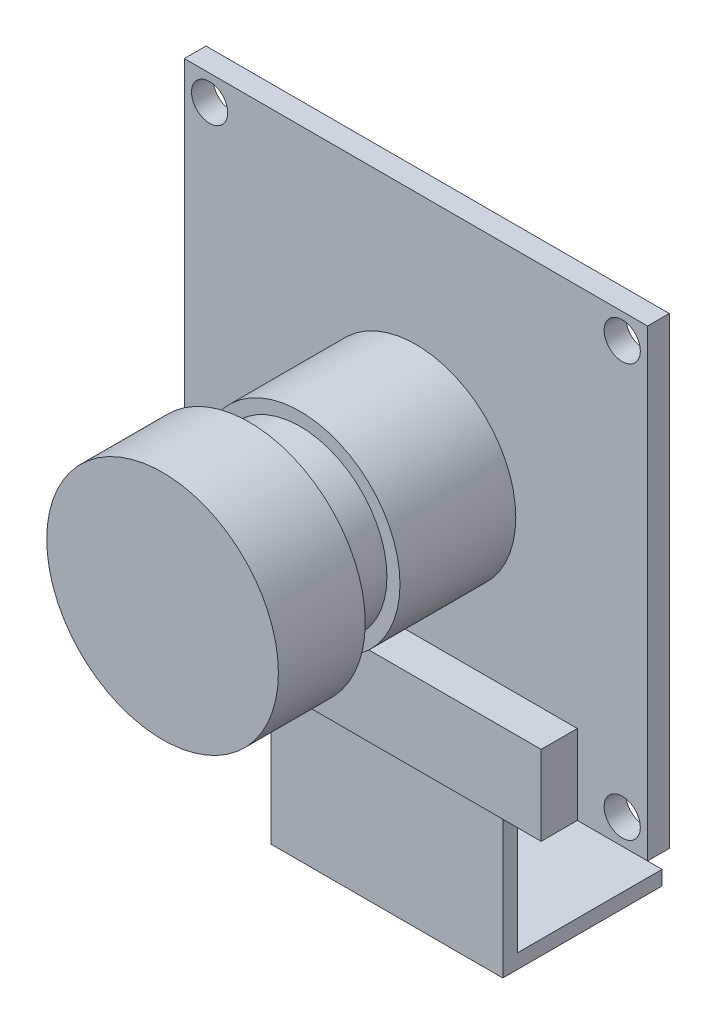
SolidWorks part; units mm, degrees
ref_plane "Спереди" through (0, 0, 0) normal (0, 0, 1) x (1, 0, 0)
ref_plane "Сверху" through (0, 0, 0) normal (0, 1, 0) x (1, 0, 0)
ref_plane "Справа" through (0, 0, 0) normal (1, 0, 0) x (0, 0, -1)
sketch "Эскиз1" plane through (0, 0, 0) normal (0, 0, 1) x (1, 0, 0)
  line L0 (0, 16) -> (0, -16) construction
  line L1 (-16, 16) -> (16, 16)
  line L2 (-16, 16) -> (-16, -16)
  line L3 (-16, -16) -> (16, -16)
  line L4 (16, 16) -> (16, -16)
  line L5 (-16, 16) -> (16, -16) construction
  line L6 (-16, -16) -> (16, 16) construction
  line L7 (-14.25, 14.25) -> (14.25, 14.25) construction
  line L8 (-14.25, 14.25) -> (-14.25, -14.25) construction
  line L9 (-14.25, -14.25) -> (14.25, -14.25) construction
  line L10 (14.25, 14.25) -> (14.25, -14.25) construction
  line L11 (-14.25, 14.25) -> (14.25, -14.25) construction
  line L12 (-14.25, -14.25) -> (14.25, 14.25) construction
  line L13 (-11.15, -10.5) -> (11.15, -10.5)
  line L14 (-11.15, -10.5) -> (-11.15, -16)
  line L15 (-11.15, -16) -> (11.15, -16)
  line L16 (11.15, -10.5) -> (11.15, -16)
  line L17 (-16, 0) -> (16, 0) construction
  circle A0 centre (0, 0) radius 6
  circle A1 centre (0, 0) radius 6.9
  circle A2 centre (0, 0) radius 8
  circle A4 centre (14.25, 14.25) radius 1.25
  circle A5 centre (14.25, -14.25) radius 1.25
  circle A6 centre (-14.25, -14.25) radius 1.25
  circle A7 centre (-14.25, 14.25) radius 1.25
  circle A9 centre (9.5, 0) radius 1.5
  circle A10 centre (-9.5, 0) radius 1.5
  point P0 (0, 0)
  point P6 (0, 0)
  point P23 (0, -16)
  point P34 (0, 0)
  dimension "D3" = 22.3
  dimension "D5" = 2.5
  dimension "D7" = 13.8
  dimension "D8" = 12
  dimension "D9" = 16
  dimension "D10" = 3
  dimension "D1" = 32
  dimension "D2" = 5.5
  dimension "D4" = 28.5
  dimension "D11" = 6.5
  dimension "D6" = 4
extrude "Плата камеры" add sketch "Эскиз1" along normal blind 1.5 contours L13 L16 L3 L4 L1 L2 L14 A7 A6 A5 A4 A2 | L16 L13 L14 L3 | A2 A1 | A1 A0 | A0 | A10 | A9 region at (0, 15.5475, 0) region at (0, -13.25, 0) region at (0, 0, 0) region at (-6.7048, 0, 0) region at (0, -7.7737, 0) region at (-9.5, 0, 0)
extrude "Гнездо шлейфа" add sketch "Эскиз1<3>" along normal blind 2.5 from surface contours L16 L13 L14 L3 region at (0, -13.25, 0) starting at face at (0, 0, 1.5)
sketch "Эскиз1<3>" plane through (0, 0, 0) normal (0, 0, 1) x (1, 0, 0) same geometry as "Эскиз1"
extrude "Основа объектива" add sketch "Эскиз1<4>" along normal blind 8 from surface contours A1 A0 | A0 region at (0, 0, 0) region at (-6.7048, 0, 0) starting at face at (-13, 14.25, 1.5)
sketch "Эскиз1<4>" plane through (0, 0, 0) normal (0, 0, 1) x (1, 0, 0) same geometry as "Эскиз1"
extrude "Резьбовая часть" add sketch "Эскиз1<5>" along normal blind 3.5 from surface contours A0 region at (0, 0, 0) starting at face at (6.9, 0, 9.5)
sketch "Эскиз1<5>" plane through (0, 0, 0) normal (0, 0, 1) x (1, 0, 0) same geometry as "Эскиз1"
extrude "Объектив(со стеклом)" add sketch "Эскиз1<6>" along normal blind 6 from surface contours A2 A1 | A1 A0 | A0 region at (0, 0, 0) region at (-6.7048, 0, 0) region at (0, -7.7737, 0) starting at face at (6, 0, 13)
sketch "Эскиз1<6>" plane through (0, 0, 0) normal (0, 0, 1) x (1, 0, 0) same geometry as "Эскиз1"
extrude "Болты крепления объектива" add sketch "Эскиз1<7>" against normal blind 0.5 contours A9 | A10 region at (-9.5, 0, 0) region at (9.5, 0, 0)
sketch "Эскиз1<7>" plane through (0, 0, 0) normal (0, 0, 1) x (1, 0, 0) same geometry as "Эскиз1"
sketch "Эскиз2" plane through (0, -16, 0) normal (0, -1, 0) x (1, 0, 0)
  line L0 (-16, 0) -> (16, 0) construction
  line L1 (-8, 3.5) -> (8, 3.5)
  line L2 (-8, 3.5) -> (-8, 2.5)
  line L3 (-8, 2.5) -> (8, 2.5)
  line L4 (8, 3.5) -> (8, 2.5)
  line L5 (-8, 3.5) -> (8, 2.5) construction
  line L6 (-8, 2.5) -> (8, 3.5) construction
  point P0 (0, 3)
  dimension "D1" = 16
  dimension "D2" = 1
  dimension "D3" = 2.5
extrude "Шлейф" add sketch "Эскиз2" along normal blind 10 contours L4 L1 L2 L3 region at (0, -16, 3)
sketch "Эскиз3" plane through (0, 0, 2.5) normal (0, 0, -1) x (-1, 0, 0)
  line L0 (-8, -26) -> (-8, -16) construction
  line L1 (-8, -25) -> (8, -25)
  line L2 (-8, -25) -> (-8, -26)
  line L3 (-8, -26) -> (8, -26)
  line L4 (8, -25) -> (8, -26)
  line M3 (-8, -16) -> (-8, -26)
  line M4 (-8, -26) -> (8, -26)
  line M5 (8, -26) -> (8, -16)
  dimension "D1" = 1
extrude "Загиб шлейфа" add sketch "Эскиз3" along normal blind 10 contours L1 M3 M4 M5 region at (0, -25.5, 2.5)
